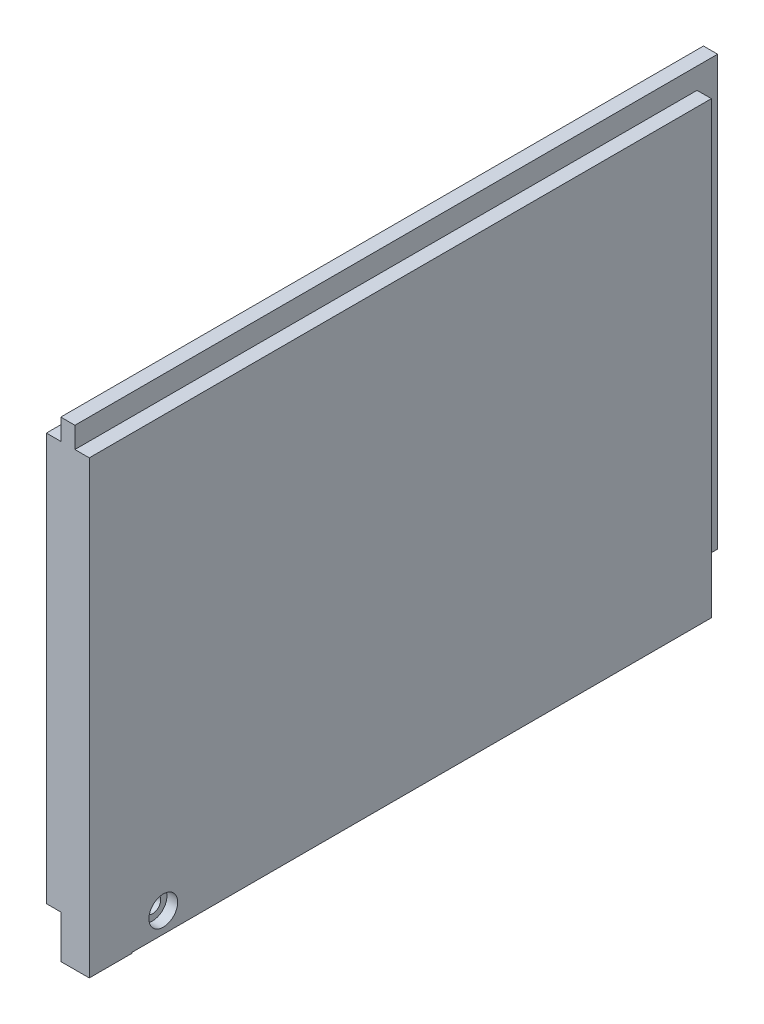
SolidWorks part; units mm, degrees
ref_plane "Front Plane" through (0, 0, 0) normal (1, 0, 0) x (0, 1, 0)
ref_plane "Top Plane" through (0, 0, 0) normal (0, 0, 1) x (0, 1, 0)
ref_plane "Right Plane" through (0, 0, 0) normal (0, 1, 0) x (-1, 0, 0)
sketch "Sketch2" plane through (0, 0, 0) normal (1, 0, 0) x (0, 1, 0)
  line L1 (0, 0) -> (95, 0)
  line L2 (0, 0) -> (0, 145)
  line L3 (0, 145) -> (95, 145)
  line L4 (95, 0) -> (95, 145)
  dimension "D1" = 95
  dimension "D2" = 145
extrude "Boss-Extrude1" add sketch "Sketch2" along normal blind 10
sketch "Sketch3" plane through (0, 95, 0) normal (0, 1, 0) x (-1, 0, 0)
  line L1 (-10, 0) -> (-6.65, 0) construction
  line L2 (-10, 0) -> (-10, -4.8) construction
  line L3 (-10, -4.8) -> (-6.65, -4.8) construction
  line L4 (-6.65, 0) -> (-6.65, -4.8) construction
  line L5 (0, 0) -> (-3.35, 0) construction
  line L6 (0, 0) -> (0, -4.8) construction
  line L7 (0, -4.8) -> (-3.35, -4.8) construction
  line L8 (-3.35, 0) -> (-3.35, -4.8) construction
  line L9 (-6.65, -4.8) -> (-3.35, -4.8)
  line L10 (-6.65, -4.8) -> (-6.65, 0)
  line L11 (-6.65, 0) -> (-3.35, 0)
  line L12 (-3.35, -4.8) -> (-3.35, 0)
  dimension "D1" = 3.35
  dimension "D2" = 3.35
  dimension "D3" = 4.8
extrude "Boss-Extrude3" add sketch "Sketch3" against normal up to surface (95 mm away) up to face at (5, 0, 72.5)
sketch "Sketch4" plane through (0, 95, 0) normal (0, 1, 0) x (-1, 0, 0)
  line L1 (-10, 145) -> (-6.65, 145) construction
  line L2 (-10, 145) -> (-10, -4.8) construction
  line L3 (-10, -4.8) -> (-6.65, -4.8) construction
  line L4 (-6.65, 145) -> (-6.65, -4.8) construction
  line L5 (-3.35, -4.8) -> (0, -4.8) construction
  line L6 (-3.35, -4.8) -> (-3.35, 145) construction
  line L7 (-3.35, 145) -> (0, 145) construction
  line L8 (0, -4.8) -> (0, 145) construction
  line L9 (-3.35, 145) -> (-6.65, 145)
  line L10 (-3.35, 145) -> (-3.35, -4.8)
  line L11 (-3.35, -4.8) -> (-6.65, -4.8)
  line L12 (-6.65, 145) -> (-6.65, -4.8)
  dimension "D1" = 3.3
extrude "Boss-Extrude4" add sketch "Sketch4" along normal blind 4.9
sketch "Sketch5" plane through (0, 0, 0) normal (0, -1, 0) x (1, 0, 0)
  line L0 (3.35, 0) -> (0, 0) construction
  line L1 (0, 145) -> (3.35, 145)
  line L2 (0, 145) -> (0, 0)
  line L3 (0, 0) -> (3.35, 0)
  line L4 (3.35, 145) -> (3.35, 0)
  line L6 (3.35, 0) -> (10, 0)
  line L7 (3.35, 0) -> (3.35, 145)
  line L8 (3.35, 145) -> (10, 145)
  line L9 (10, 0) -> (10, 145)
  line M6 (6.65, 0) -> (10, 0)
  line M7 (10, 0) -> (10, 145)
  line M8 (10, 145) -> (0, 145)
  dimension "D1" = 3.35
  dimension "D2" = 6.65
extrude "Boss-Extrude5" add sketch "Sketch5" along normal blind 10 contours L4 L6 M6 M7 M8 region at (6.675, 0, 72.5)
sketch "Sketch6" plane through (10, 0, 0) normal (1, 0, 0) x (0, 1, 0)
  line L1 (-10, 145) -> (-5, 145) construction
  line L2 (-10, 145) -> (-10, 127.75) construction
  line L3 (-10, 127.75) -> (-5, 127.75) construction
  line L4 (-5, 145) -> (-5, 127.75) construction
  circle A0 centre (-5, 127.75) radius 1.9
  dimension "D3" = 3.8
  dimension "D1" = 17.25
  dimension "D2" = 5
extrude "Cut-Extrude1" cut sketch "Sketch6" against normal up to next
sketch "Sketch8" plane through (10, 0, 0) normal (1, 0, 0) x (0, 1, 0)
  circle A0 centre (-5, 127.75) radius 3.35
  dimension "D1" = 6.7
extrude "Cut-Extrude3" cut sketch "Sketch8" against normal blind 2.5
sketch "Sketch7" plane through (10, 0, 0) normal (1, 0, 0) x (0, 1, 0)
  line L0 (-10, 0) -> (-10, 145) construction
  line L1 (-10, 135) -> (-9.8, 135)
  line L2 (-10, 135) -> (-10, 0)
  line L3 (-10, 0) -> (-9.8, 0)
  line L4 (-9.8, 135) -> (-9.8, 0)
  line L5 (-10, 0) -> (95, 0) construction
extrude "Cut-Extrude2" cut sketch "Sketch7" against normal up to next
sketch "Sketch9" plane through (0, 0, 0) normal (-1, 0, 0) x (0, -1, 0)
  line L0 (-90, 5) -> (-90, 140)
  line L1 (-95, 0) -> (0, 0)
  line L2 (-95, 0) -> (-95, 145)
  line L3 (-95, 145) -> (0, 145)
  line L4 (0, 0) -> (0, 145)
  line L5 (-90, 140) -> (-5, 140)
  line L6 (-5, 5) -> (-5, 140)
  line L7 (-90, 5) -> (-5, 5)
  dimension "D1" = 5
extrude "Cut-Extrude4" cut sketch "Sketch9" against normal blind 5 contours L0 L7 L6 L5 region at (0, 47.5, 72.5)
chamfer "Chamfer1" distance 5 distance2 2.5 4 edges at (0, 47.5, 5) (0, 5, 72.5) (0, 90, 72.5) (0, 47.5, 140) first distance on face at (2.5, 47.5, 5) first distance on face at (2.5, 5, 72.5) first distance on face at (2.5, 90, 72.5) first distance on face at (2.5, 47.5, 140)
equation "\"whitekey_cutout_length\"= 101.5"
equation "\"whitekey_spacing\"=1.25"
equation "\"key_mount_recess_length\"=50"
equation "\"key_mount_recess_height\"=12.5"
equation "\"key_mount_recess_depth\"=1.5"
equation "\"wall_thickness\"=10"
equation "\"guide_brace_height\"=20"
equation "\"guide_brace_thickness\"=2"
equation "\"dowel_recess_depth\"=10"
equation "\"dowel_recess_offset\"=3.25"
equation "\"dowel_insert_tolerance\"=0.1"
equation "\"base_mount_height\"=40"
equation "\"base_rear_length\"=80"
equation "\"base_front_length\"=111.5"
equation "\"screw_hole_wall_offset\"=7.25"
equation "\"screw_hole_edge_inset\"=\"dowel_recess_depth\"/2"
equation "\"screw_hole_diameter\"=3.8"
equation "\"screw_head_hole_diameter\"=6.7"
equation "\"screw_nut_hole_side_len\"=3.5"
equation "\"screw_nut_recess_offset\"=0.35"
equation "\"screw_head_and_nut_recess_depth\"=2.5"
equation "\"screw_shaft_diameter\"=3.5"
equation "\"switch_board_width\"=30"
equation "\"switch_board_thickness\"=1.6"
equation "\"switch_board_wall_offset\"=11.5"
equation "\"heatset_insert_hole_diameter\"=4.8"
equation "\"heatset_insert_hole_depth\"=3.8"
equation "\"front_rear_panel_width\"=23.75"
equation "\"front_panel_height\"=24"
equation "\"front_rear_panel_recess_depth\"=5"
equation "\"rod_diameter\"=5"
equation "\"rod_head_diameter\"=8"
equation "\"rod_length_adj\"=0.5"
equation "\"rod_insert_length\"=2.8"
equation "\"switch_black_key_mount_height\"=8"
equation "\"switch_white_key_mount_height\"=3"
equation "\"side_panel_depth\"=35"
equation "\"interface_panel_height\"=135"
equation "\"interface_panel_roof_length\"=50"
equation "\"D1@Sketch2\"=\"front_rear_panel_width\"*4"
equation "\"D2@Sketch2\"=\"interface_panel_height\"+\"wall_thickness\""
equation "\"D1@Boss-Extrude1\"=\"wall_thickness\""
equation "\"D1@Sketch3\"=\"dowel_recess_offset\"+\"dowel_insert_tolerance\""
equation "\"D2@Sketch3\"=\"dowel_recess_offset\"+\"dowel_insert_tolerance\""
equation "\"D3@Sketch3\"=\"front_rear_panel_recess_depth\"-\"dowel_insert_tolerance\"*2"
equation "\"D1@Boss-Extrude4\"=\"front_rear_panel_recess_depth\"-\"dowel_insert_tolerance\""
equation "\"D1@Sketch5\"=\"dowel_recess_offset\"+\"dowel_insert_tolerance\""
equation "\"D1@Boss-Extrude5\"=\"dowel_recess_depth\""
equation "\"D1@Sketch6\"=\"wall_thickness\"+\"screw_hole_wall_offset\""
equation "\"D2@Sketch6\"=\"screw_hole_edge_inset\""
equation "\"D3@Sketch6\"=\"screw_hole_diameter\""
equation "\"D1@Sketch7\"=\"dowel_insert_tolerance\"*2"
equation "\"D1@Sketch8\"=\"screw_head_hole_diameter\""
equation "\"D1@Cut-Extrude3\"=\"screw_head_and_nut_recess_depth\""
equation "\"D1@Cut-Extrude4\"=\"wall_thickness\"/2"
